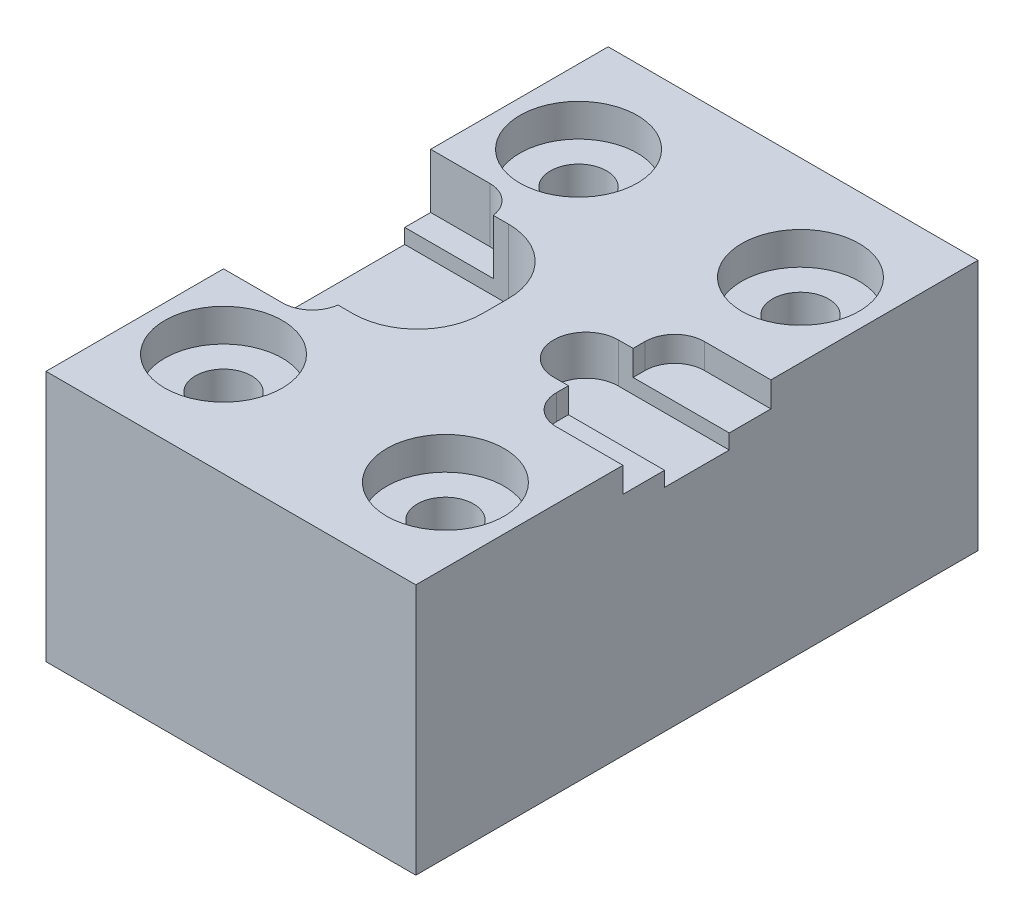
SolidWorks part; units mm, degrees
material "6063-T5"
ref_plane "Front Plane" through (0, 0, 0) normal (0, 0, 1) x (1, 0, 0)
ref_plane "Top Plane" through (0, 0, 0) normal (0, 1, 0) x (1, 0, 0)
ref_plane "Right Plane" through (0, 0, 0) normal (1, 0, 0) x (0, 0, -1)
sketch "Sketch1" plane through (0, 0, 0) normal (0, 1, 0) x (1, 0, 0)
  line L1 (-18493.9467, 11317.1913) -> (-18468.9467, 11317.1913)
  line L2 (-18493.9467, 11317.1913) -> (-18493.9467, 11279.1913)
  line L3 (-18493.9467, 11279.1913) -> (-18468.9467, 11279.1913)
  line L4 (-18468.9467, 11317.1913) -> (-18468.9467, 11279.1913)
  dimension "D1" = 25
  dimension "D2" = 38
extrude "Boss-Extrude1" add sketch "Sketch1" along normal blind 17
sketch "Sketch2" plane through (0, 17, 0) normal (0, 1, 0) x (1, 0, 0)
  line L0 (-18493.9467, 11298.1913) -> (-18468.9467, 11298.1913)
  line L1 (-18493.9467, 11317.1913) -> (-18493.9467, 11279.1913) construction
  line L2 (-18468.9467, 11279.1913) -> (-18468.9467, 11317.1913) construction
  line L3 (-18491.9467, 11305.1913) -> (-18493.9467, 11305.1913)
  line L4 (-18489.9467, 11291.1913) -> (-18491.9467, 11291.1913)
  line L5 (-18487.9467, 11293.1913) -> (-18487.9467, 11303.1913)
  line L6 (-18489.9467, 11305.1913) -> (-18491.9467, 11305.1913)
  line L7 (-18493.9467, 11300.1913) -> (-18493.9467, 11314.1913)
  line L8 (-18487.9467, 11291.1913) -> (-18493.9467, 11305.1913) construction
  line L9 (-18487.9467, 11305.1913) -> (-18493.9467, 11291.1913) construction
  line L10 (-18470.9467, 11293.1913) -> (-18473.4467, 11293.1913)
  line L11 (-18468.9467, 11293.1913) -> (-18468.9467, 11303.1913)
  line L12 (-18470.9467, 11303.1913) -> (-18473.4467, 11303.1913)
  line L13 (-18475.4467, 11295.1913) -> (-18475.4467, 11301.1913)
  line L14 (-18468.9467, 11293.1913) -> (-18475.4467, 11303.1913) construction
  line L15 (-18468.9467, 11303.1913) -> (-18475.4467, 11293.1913) construction
  line L16 (-18491.9467, 11291.1913) -> (-18493.9467, 11291.1913)
  line L17 (-18470.9467, 11303.1913) -> (-18468.9467, 11303.1913)
  line L18 (-18470.9467, 11293.1913) -> (-18468.9467, 11293.1913)
  line L19 (-18488.9467, 11286.1913) -> (-18488.9467, 11310.1913)
  line L20 (-18488.9467, 11286.1913) -> (-18473.9467, 11286.1913)
  line L21 (-18488.9467, 11310.1913) -> (-18473.9467, 11310.1913)
  line L22 (-18473.9467, 11286.1913) -> (-18473.9467, 11310.1913)
  line L23 (-18488.9467, 11286.1913) -> (-18473.9467, 11310.1913) construction
  line L24 (-18488.9467, 11310.1913) -> (-18473.9467, 11286.1913) construction
  arc A0 (-18489.9467, 11291.1913) -> (-18487.9467, 11293.1913) centre (-18489.9467, 11293.1913) ccw
  arc A1 (-18487.9467, 11303.1913) -> (-18489.9467, 11305.1913) centre (-18489.9467, 11303.1913) ccw
  arc A5 (-18473.4467, 11303.1913) -> (-18475.4467, 11301.1913) centre (-18473.4467, 11301.1913) ccw
  arc A6 (-18473.4467, 11293.1913) -> (-18475.4467, 11295.1913) centre (-18473.4467, 11295.1913) cw
  point P6 (-18490.9467, 11298.1913)
  point P11 (-18472.1967, 11298.1913)
  point P16 (-18492.9467, 11291.1913)
  point P25 (-18481.4467, 11298.1913)
  line M12 (-18493.9467, 11317.1913) -> (-18493.9467, 11279.1913)
  dimension "D7" = 2
  dimension "D8" = 5
  dimension "D9" = 5
  dimension "D10" = 5
  dimension "D1" = 12.5
  dimension "D2" = 0
  dimension "D3" = 6
  dimension "D4" = 0
  dimension "D5" = 10
  dimension "D6" = 14
  dimension "D11" = 5
extrude "Cut-Extrude3" cut sketch "Sketch2" against normal offset from surface (3.7 mm away) 13.3 contours L5 A1 L6 L3 L0 M12 | L4 A0 L5 L0 L16 M12 | L5 A1 L19 L0 | L19 A0 L5 L0 region at (-18491.4523, 17, -11301.6828) region at (-18491.4523, 17, -11294.6998) region at (-18488.4645, 17, -11301.3181) region at (-18488.4645, 17, -11295.0644) up to face at (-18481.4467, 0, -11298.1913)
extrude "Cut-Extrude4" cut sketch "Sketch2<6>" against normal offset from surface (1.7 mm away) 15.3 contours L12 A5 L13 L0 L11 | A6 L10 L11 L0 L13 | L22 A5 L13 L0 | A6 L22 L0 L13 region at (-18474.6562, 17, -11300.4302) region at (-18474.6562, 17, -11295.9523) region at (-18471.4457, 17, -11300.6902) region at (-18471.4457, 17, -11295.6923) up to face at (-18481.4467, 0, -11298.1913)
sketch "Sketch2<6>" plane through (0, 17, 0) normal (0, 1, 0) x (1, 0, 0) same geometry as "Sketch2"
hole_wizard "CBORE for #6 Binding Head Machine Screw1" positions "Sketch10" profile "Sketch11" counterbore size "#6" standard "ANSI Inch" end condition through all
sketch "Sketch10" plane through (0, 17, 0) normal (0, 1, 0) x (1, 0, 0)
  point P0 (-18488.9467, 11310.1913)
  point P3 (-18473.9467, 11310.1913)
  point P6 (-18473.9467, 11286.1913)
  point P9 (-18488.9467, 11286.1913)
sketch "Sketch11" plane through (-18488.9467, 17, -11310.1913) normal (1, 0, 0) x (0, 0, 1)
  line L0 (0, 0) -> (0, 17)
  line L1 (0, 17) -> (1.8986, 17)
  line L3 (1.8986, 17) -> (1.8986, 2.2098)
  line L4 (1.8986, 2.2098) -> (3.9687, 2.2098)
  line L5 (3.9687, 2.2098) -> (3.9687, 0)
  line L7 (3.9687, 0) -> (0, 0)
  line L11 (0, -6.35) -> (0, 107.95) construction
  dimension "Thru Hole Dia." = 3.7973
  dimension "Thru Hole Depth" = 17
  dimension "C'Bore Dia." = 7.9375
  dimension "C'Bore Depth" = 2.2098
sketch "Sketch12" plane through (0, 17, 0) normal (0, 1, 0) x (1, 0, 0)
  line L0 (-18468.9467, 11293.1913) -> (-18468.9467, 11303.1913) construction
  line L1 (-18476.4467, 11300.3763) -> (-18468.9467, 11300.3763)
  line L2 (-18476.4467, 11300.3763) -> (-18476.4467, 11296.0063)
  line L3 (-18476.4467, 11296.0063) -> (-18468.9467, 11296.0063)
  line L4 (-18468.9467, 11300.3763) -> (-18468.9467, 11296.0063)
  line L5 (-18493.9467, 11298.1913) -> (-18468.9467, 11298.1913) construction
  line L6 (-18487.9467, 11293.1913) -> (-18487.9467, 11303.1913) construction
  arc A0 (-18476.4467, 11300.3763) -> (-18476.4467, 11296.0063) centre (-18476.4467, 11298.1913) ccw
  point P6 (-18476.4467, 11298.1913)
  line M20 (-18475.4467, 11295.1913) -> (-18475.4467, 11301.1913)
  dimension "D1" = 0
  dimension "D2" = 4.37
  dimension "D3" = 11.5
extrude "Cut-Extrude5" cut sketch "Sketch12" against normal offset from surface (2.7 mm away) 14.3 contours L2 A0 | L2 L3 L1 M20 | L4 L1 L3 M20 region at (-18475.9467, 17, -11298.1913) region at (-18477.3741, 17, -11298.1913) region at (-18472.1967, 17, -11298.1913) up to face at (-18488.9467, 0, -11308.2926)
sketch "Sketch13" plane through (0, 17, 0) normal (0, 1, 0) x (1, 0, 0)
  line L0 (-18493.9467, 11291.1913) -> (-18493.9467, 11305.1913) construction
  line L1 (-18486.9467, 11303.4413) -> (-18493.9467, 11303.4413)
  line L2 (-18486.9467, 11303.4413) -> (-18486.9467, 11292.9413)
  line L3 (-18486.9467, 11292.9413) -> (-18493.9467, 11292.9413)
  line L4 (-18493.9467, 11303.4413) -> (-18493.9467, 11292.9413)
  line L5 (-18493.9467, 11298.1913) -> (-18468.9467, 11298.1913) construction
  line L6 (-18487.9467, 11293.1913) -> (-18487.9467, 11303.1913) construction
  line L8 (-18486.9467, 11303.4413) -> (-18486.9367, 11303.4413)
  line L9 (-18486.9467, 11303.4413) -> (-18486.9467, 11292.9413)
  line L10 (-18486.9467, 11292.9413) -> (-18486.9367, 11292.9413)
  line L11 (-18482.5767, 11299.0813) -> (-18482.5767, 11297.3013)
  arc A0 (-18486.9367, 11292.9413) -> (-18482.5767, 11297.3013) centre (-18486.9367, 11297.3013) ccw
  arc A1 (-18486.9367, 11303.4413) -> (-18482.5767, 11299.0813) centre (-18486.9367, 11299.0813) cw
  point P6 (-18486.9467, 11298.1913)
  point P17 (-18482.5767, 11303.4413)
  arc M19 (-18489.9467, 11305.1913) -> (-18487.9467, 11303.1913) centre (-18489.9467, 11303.1913) cw
  line M20 (-18487.9467, 11303.1913) -> (-18487.9467, 11293.1913)
  arc M21 (-18487.9467, 11293.1913) -> (-18489.9467, 11291.1913) centre (-18489.9467, 11293.1913) cw
  dimension "D5" = 4.36
  dimension "D1" = 0
  dimension "D2" = 10.5
  dimension "D3" = 1
  dimension "D4" = 4.37
extrude "Cut-Extrude6" cut sketch "Sketch13" against normal offset from surface (4.7 mm away) 12.3 contours A1 L8 L2 L10 A0 L11 | L1 L4 L3 M21 M20 M19 | L3 L2 L1 M19 M20 M21 region at (-18487.4469, 17, -11298.1913) region at (-18485.0237, 17, -11298.1913) region at (-18490.9469, 17, -11298.1913) up to face at (-18488.9467, 0, -11308.2926)
